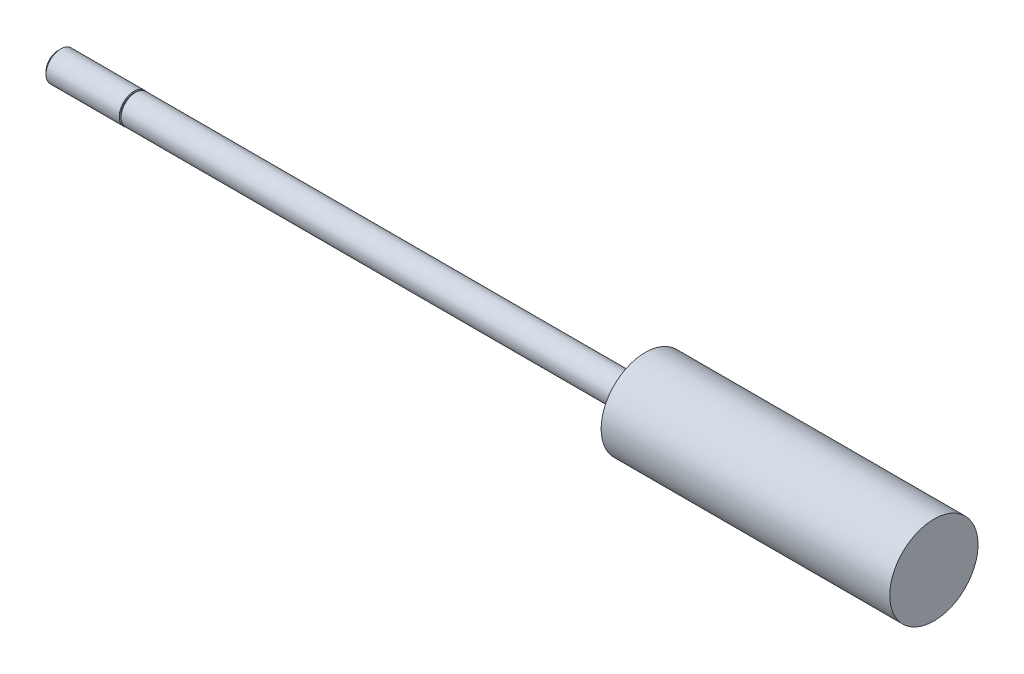
SolidWorks part; units mm, degrees
material "Cast Alloy Steel"
ref_plane "Front Plane" through (0, 0, 0) normal (0, 0, 1) x (1, 0, 0)
ref_plane "Top Plane" through (0, 0, 0) normal (0, 1, 0) x (1, 0, 0)
ref_plane "Right Plane" through (0, 0, 0) normal (1, 0, 0) x (0, 0, -1)
sketch "Sketch1" plane through (0, 0, 0) normal (0, 0, 1) x (1, 0, 0)
  line L0 (0, 0) -> (0, 2.3749)
  line L1 (0, 2.3749) -> (83.3374, 2.3749)
  line L2 (83.3374, 2.3749) -> (83.3374, 7.2199)
  line L3 (83.3374, 7.2199) -> (130.5306, 7.2199)
  line L4 (130.5306, 7.2199) -> (130.5306, 0)
  line L5 (130.5306, 0) -> (0, 0)
  line L6 (130.5306, 0) -> (0, 0) construction
revolve "Revolve1" add sketch "Sketch1" angle 360 about L6 reverse direction yes
sketch "Sketch2" plane through (0, 0, 0) normal (0, 0, 1) x (1, 0, 0)
  line L0 (-12.7, 0) -> (-12.7, 1.9406)
  line L1 (-12.7, 1.9406) -> (-12.2276, 2.413)
  line L2 (-12.2276, 2.413) -> (0, 2.413)
  line L3 (0, 2.413) -> (0, 0)
  line L4 (0, 0) -> (-12.7, 0)
  line L5 (0, 0) -> (-12.7, 0) construction
revolve "Revolve2" add sketch "Sketch2" angle 360 about L5 reverse direction yes
cosmetic thread "Cosmetic Thread1"
ref_plane "Plane1" through (0, 0, 0) normal (1, 0, 0) x (0, 0, -1)
ref_plane "Plane2" through (0, 0, 0) normal (1, 0, 0) x (0, 0, -1)
ref_plane "Plane3" through (213.868, 0, 0) normal (1, 0, 0) x (0, 0, -1)
ref_plane "Plane4" through (-12.7, 0, 0) normal (1, 0, 0) x (0, 0, -1)
sketch "Sketch3" plane through (0, 0, 0) normal (0, 0, 1) x (1, 0, 0)
  line L0 (-0.254, 2.667) -> (-0.254, 2.159)
  line L1 (-0.254, 2.159) -> (0, 2.159)
  line L2 (0, 2.159) -> (0, 2.667)
  line L3 (0, 2.667) -> (-0.254, 2.667)
  line L4 (0, 0) -> (-0.254, 0) construction
revolve "Cut-Revolve1" cut sketch "Sketch3" angle 360 about L4 reverse direction yes
ref_plane "Plane5" through (0, 0, 0) normal (1, 0, 0) x (0, 0, -1)
ref_plane "Plane6" through (-12.7, 0, 0) normal (1, 0, 0) x (0, 0, -1)
ref_plane "dia1 XY" through (0, 0, 0) normal (1, 0, 0) x (0, 0, -1)
ref_plane "dia1 XZ" through (0, 2.3749, 0) normal (0, -1, 0) x (-1, 0, 0)
ref_plane "dia1 YZ" through (0, 0, 0) normal (0, 0, -1) x (-1, 0, 0)
ref_axis "dia1 X" through (0, 2.3749, 80.9) along (0, 0, -1)
ref_axis "dia1 Y" through (0, -50, 0) along (0, 1, 0)
ref_axis "dia1 Z" through (80.9, 2.3749, 0) along (-1, 0, 0)
sketch3d "dia1"
  point P0 (0, 2.3749, 0)
ref_plane "dia12 XY" through (0, 0, 0) normal (1, 0, 0) x (0, 0, -1)
ref_plane "dia12 XZ" through (0, 0, 0) normal (0, -1, 0) x (-1, 0, 0)
ref_plane "dia12 YZ" through (0, 0, 7.8105) normal (0, 0, -1) x (-1, 0, 0)
ref_axis "dia12 X" through (0, 0, 80.9) along (0, 0, -1)
ref_axis "dia12 Y" through (0, -50, 7.8105) along (0, 1, 0)
ref_axis "dia12 Z" through (80.9, 0, 7.8105) along (-1, 0, 0)
sketch3d "dia12"
  point P0 (0, 0, 7.8105)
ref_plane "dia2 XY" through (0, 0, 0) normal (1, 0, 0) x (0, 0, -1)
ref_plane "dia2 XZ" through (0, -2.3749, 0) normal (0, -1, 0) x (-1, 0, 0)
ref_plane "dia2 YZ" through (0, 0, 0) normal (0, 0, -1) x (-1, 0, 0)
ref_axis "dia2 X" through (0, -2.3749, 80.9) along (0, 0, -1)
ref_axis "dia2 Y" through (0, -50, 0) along (0, 1, 0)
ref_axis "dia2 Z" through (80.9, -2.3749, 0) along (-1, 0, 0)
sketch3d "dia2"
  point P0 (0, -2.3749, 0)
ref_plane "dia22 XY" through (0, 0, 0) normal (1, 0, 0) x (0, 0, -1)
ref_plane "dia22 XZ" through (0, 0, 0) normal (0, -1, 0) x (-1, 0, 0)
ref_plane "dia22 YZ" through (0, 0, -7.8105) normal (0, 0, -1) x (-1, 0, 0)
ref_axis "dia22 X" through (0, 0, 80.9) along (0, 0, -1)
ref_axis "dia22 Y" through (0, -50, -7.8105) along (0, 1, 0)
ref_axis "dia22 Z" through (80.9, 0, -7.8105) along (-1, 0, 0)
sketch3d "dia22"
  point P0 (0, 0, -7.8105)
ref_plane "rl1 XY" through (-12.7, 0, 0) normal (1, 0, 0) x (0, 0, -1)
ref_plane "rl1 XZ" through (0, 0, 0) normal (0, -1, 0) x (-1, 0, 0)
ref_plane "rl1 YZ" through (0, 0, 0) normal (0, 0, -1) x (-1, 0, 0)
ref_axis "rl1 X" through (-12.7, 0, 80.9) along (0, 0, -1)
ref_axis "rl1 Y" through (-12.7, -50, 0) along (0, 1, 0)
ref_axis "rl1 Z" through (80.9, 0, 0) along (-1, 0, 0)
sketch3d "rl1"
  point P0 (-12.7, 0, 0)
ref_plane "rl2 XY" through (0, 0, 0) normal (1, 0, 0) x (0, 0, -1)
ref_plane "rl2 XZ" through (0, 0, 0) normal (0, -1, 0) x (-1, 0, 0)
ref_plane "rl2 YZ" through (0, 0, 0) normal (0, 0, -1) x (-1, 0, 0)
ref_axis "rl2 X" through (0, 0, 80.9) along (0, 0, -1)
ref_axis "rl2 Y" through (0, -50, 0) along (0, 1, 0)
ref_axis "rl2 Z" through (80.9, 0, 0) along (-1, 0, 0)
sketch3d "rl2"
  point P0 (0, 0, 0)
ref_plane "rod_cp XY" through (0, 0, 0) normal (1, 0, 0) x (0, 0, -1)
ref_plane "rod_cp XZ" through (0, 0, 0) normal (0, -1, 0) x (-1, 0, 0)
ref_plane "rod_cp YZ" through (0, 0, 0) normal (0, 0, -1) x (-1, 0, 0)
ref_axis "rod_cp X" through (0, 0, 80.9) along (0, 0, -1)
ref_axis "rod_cp Y" through (0, -50, 0) along (0, 1, 0)
ref_axis "rod_cp Z" through (80.9, 0, 0) along (-1, 0, 0)
sketch3d "rod_cp"
  point P0 (0, 0, 0)
ref_plane "thd1 XY" through (-12.7, 0, 0) normal (1, 0, 0) x (0, 0, -1)
ref_plane "thd1 XZ" through (0, 2.413, 0) normal (0, -1, 0) x (-1, 0, 0)
ref_plane "thd1 YZ" through (0, 0, 0) normal (0, 0, -1) x (-1, 0, 0)
ref_axis "thd1 X" through (-12.7, 2.413, 80.9) along (0, 0, -1)
ref_axis "thd1 Y" through (-12.7, -50, 0) along (0, 1, 0)
ref_axis "thd1 Z" through (80.9, 2.413, 0) along (-1, 0, 0)
sketch3d "thd1"
  point P0 (-12.7, 2.413, 0)
ref_plane "thd2 XY" through (-12.7, 0, 0) normal (1, 0, 0) x (0, 0, -1)
ref_plane "thd2 XZ" through (0, -2.413, 0) normal (0, -1, 0) x (-1, 0, 0)
ref_plane "thd2 YZ" through (0, 0, 0) normal (0, 0, -1) x (-1, 0, 0)
ref_axis "thd2 X" through (-12.7, -2.413, 80.9) along (0, 0, -1)
ref_axis "thd2 Y" through (-12.7, -50, 0) along (0, 1, 0)
ref_axis "thd2 Z" through (80.9, -2.413, 0) along (-1, 0, 0)
sketch3d "thd2"
  point P0 (-12.7, -2.413, 0)
ref_plane "to_rod_clevis XY" through (-12.7, 0, 0) normal (1, 0, 0) x (0, 0, -1)
ref_plane "to_rod_clevis XZ" through (0, 0, 0) normal (0, -1, 0) x (-1, 0, 0)
ref_plane "to_rod_clevis YZ" through (0, 0, 0) normal (0, 0, -1) x (-1, 0, 0)
ref_axis "to_rod_clevis X" through (-12.7, 0, 80.9) along (0, 0, -1)
ref_axis "to_rod_clevis Y" through (-12.7, -50, 0) along (0, 1, 0)
ref_axis "to_rod_clevis Z" through (80.9, 0, 0) along (-1, 0, 0)
sketch3d "to_rod_clevis"
  point P0 (-12.7, 0, 0)
